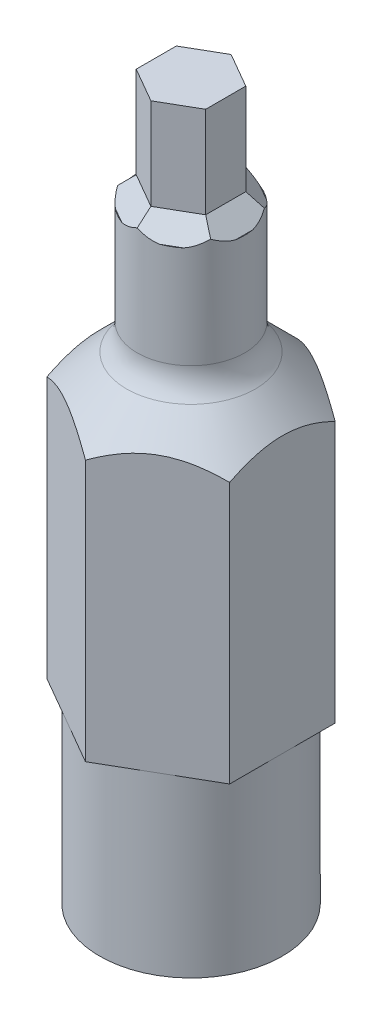
SolidWorks part; units mm, degrees
ref_plane "Front Plane" through (0, 0, 0) normal (0, 0, 1) x (1, 0, 0)
ref_plane "Top Plane" through (0, 0, 0) normal (0, 1, 0) x (1, 0, 0)
ref_plane "Right Plane" through (0, 0, 0) normal (1, 0, 0) x (0, 0, -1)
sketch "Sketch1" plane through (0, 0, 0) normal (0, 1, 0) x (1, 0, 0)
  line L0 (0, 0) -> (0, 3.6662)
  line L1 (0, 3.6662) -> (-3.175, 1.8331)
  line L2 (-3.175, 1.8331) -> (-3.175, -1.8331)
  line L3 (-3.175, -1.8331) -> (0, -3.6662)
  line L4 (0, -3.6662) -> (3.175, -1.8331)
  line L5 (3.175, -1.8331) -> (3.175, 1.8331)
  line L6 (3.175, 1.8331) -> (0, 3.6662)
  circle A0 centre (0, 0) radius 3.175 construction
  dimension "D1" = 6.35
extrude "Boss-Extrude1" add sketch "Sketch1" along normal blind 8.3312 contours L5 L6 L1 L2 L3 L4 region at (1.539, 0, -2.6656)
sketch "Sketch2" plane through (0, 0, 0) normal (0, -1, 0) x (1, 0, 0)
  circle A0 centre (0, 0) radius 3.175
  dimension "D1" = 6.35
extrude "Boss-Extrude2" add sketch "Sketch2" along normal blind 6.096
sketch "Sketch3" plane through (0, 8.3312, 0) normal (0, 1, 0) x (1, 0, 0)
  circle A0 centre (0, 0) radius 1.8669
  dimension "D1" = 3.7338
extrude "Boss-Extrude3" add sketch "Sketch3" along normal blind 6.604
sketch "Sketch4" plane through (0, 14.9352, 0) normal (0, 1, 0) x (1, 0, 0)
  line L0 (0, 0) -> (0, 1.3931)
  line L1 (0, 1.3931) -> (-1.2065, 0.6966)
  line L2 (-1.2065, 0.6966) -> (-1.2065, -0.6966)
  line L3 (-1.2065, -0.6966) -> (0, -1.3931)
  line L4 (0, -1.3931) -> (1.2065, -0.6966)
  line L5 (1.2065, -0.6966) -> (1.2065, 0.6966)
  line L6 (1.2065, 0.6966) -> (0, 1.3931)
  circle A0 centre (0, 0) radius 1.2065 construction
  dimension "D1" = 2.413
extrude "Boss-Extrude4" add sketch "Sketch4" along normal blind 3.81 contours L5 L6 L1 L2 L3 L4 region at (0.5848, 14.9352, -1.0129)
chamfer "Chamfer1" distance 0.635 angle 45 6 edges at (0.6032, 14.9352, -1.0449) (1.2065, 14.9352, 0) (-0.6033, 14.9352, -1.0449) (-1.2065, 14.9352, 0) (-0.6033, 14.9352, 1.0449) (0.6032, 14.9352, 1.0449)
chamfer "Chamfer2" distance 2.54 angle 45 1 edges at (0, 8.3312, 1.8669)
fillet "Fillet2" radius 1.27 1 edges at (0, 10.8712, 1.8669)
